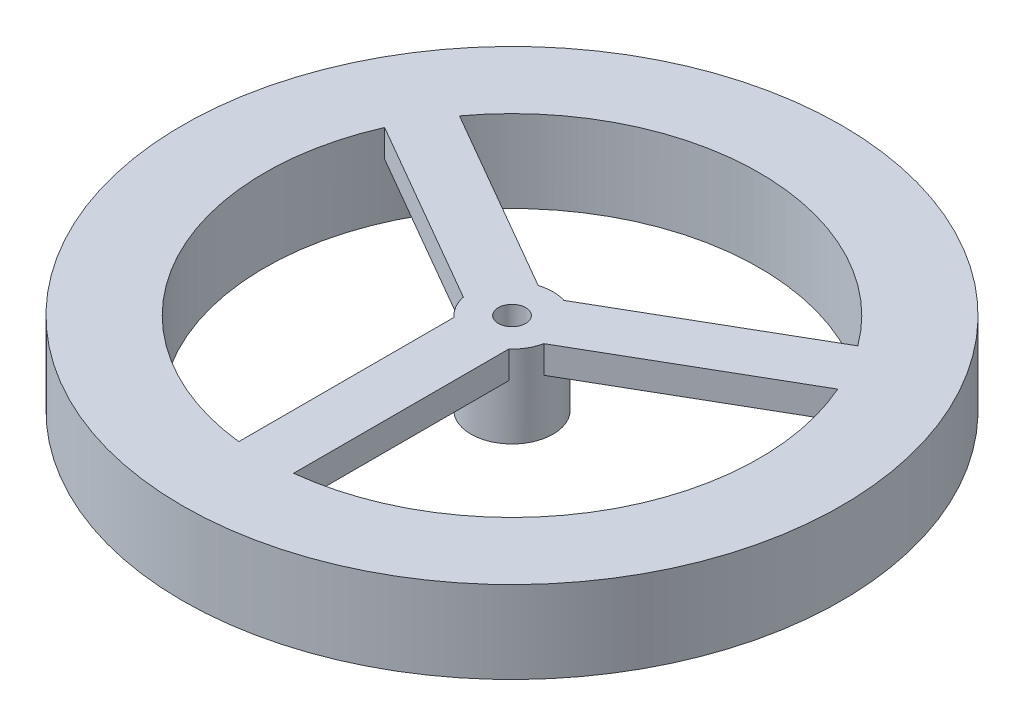
SolidWorks part; units mm, degrees
material "Pure Lead"
ref_plane "Front Plane" through (0, 0, 0) normal (0, 0, 1) x (1, 0, 0)
ref_plane "Top Plane" through (0, 0, 0) normal (0, 1, 0) x (1, 0, 0)
ref_plane "Right Plane" through (0, 0, 0) normal (1, 0, 0) x (0, 0, -1)
sketch "Sketch1" plane through (0, 0, 0) normal (0, 1, 0) x (1, 0, 0)
  circle A0 centre (0, 0) radius 60.124
  circle A1 centre (0, 0) radius 45.124
  circle A2 centre (0, 0) radius 2.5
  circle A3 centre (0, 0) radius 7.5
  dimension "D1" = 5
  dimension "D2" = 5
  dimension "D3" = 90.248
  dimension "D4" = 15
extrude "Boss-Extrude1" add sketch "Sketch1" against normal blind 15 contours A0 A1 | A3 A2 region at (-58.4234, 0, 0) region at (-7.2879, 0, 0)
sketch "Sketch2" plane through (0, 0, 0) normal (0, 1, 0) x (1, 0, 0)
  line L0 (0, 0) -> (5, -5.5902) construction
  line L1 (-5, -5.5902) -> (5, -5.5902)
  line L2 (-5, -5.5902) -> (-5, -45.124)
  line L3 (-5, -45.124) -> (5, -45.124)
  line L4 (5, -5.5902) -> (5, -45.124)
  line L5 (0, 0) -> (5, -44.8461) construction
  line L6 (-13.4233, 0) -> (15.5933, 0) construction
  line L7 (0, 0) -> (5, 44.8461) construction
  line L8 (0, 0) -> (5, 5.5902) construction
  circle A0 centre (0, 0) radius 7.5 construction
  circle A1 centre (0, 0) radius 45.124 construction
  dimension "D1" = 10
  dimension "D2" = 96.379
  dimension "D3" = 167.276
extrude "Boss-Extrude2" add sketch "Sketch2" against normal blind 5
pattern_circular "CirPattern1" count 3 over 360 about axis through (0, -15, 0) along (0, 1, 0) of "Boss-Extrude2" reverse direction yes
